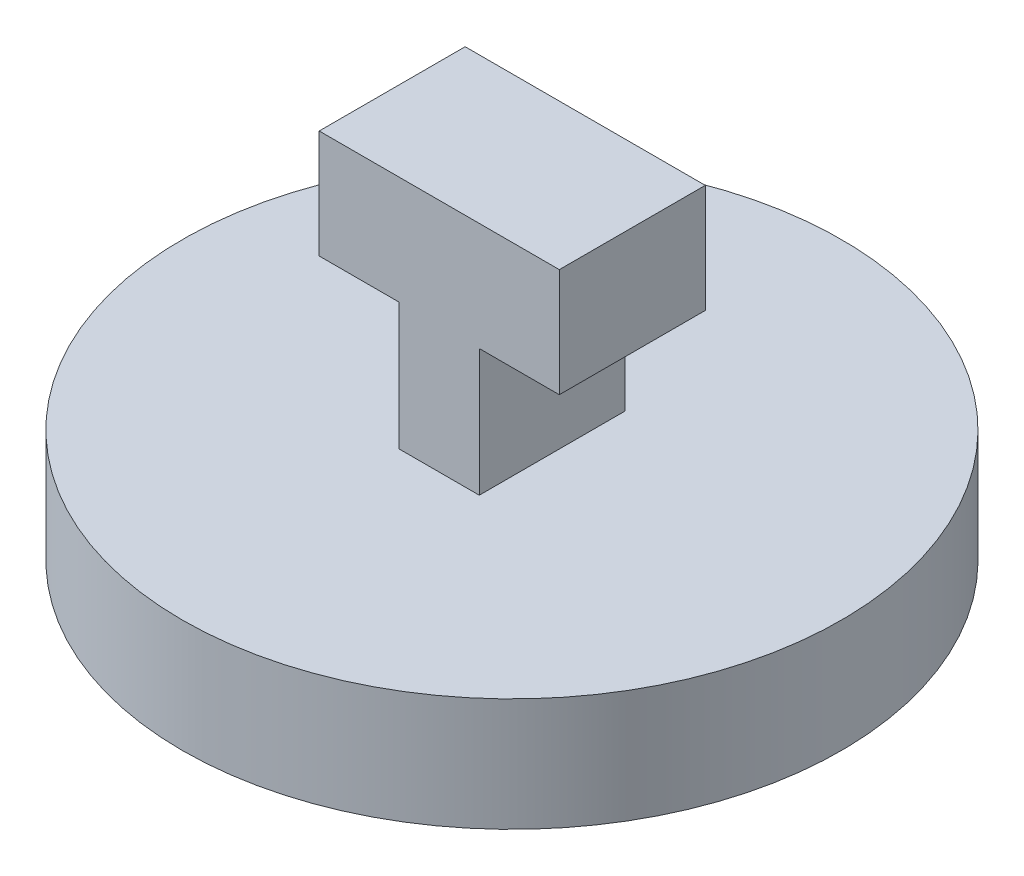
SolidWorks part; units mm, degrees
ref_plane "Front Plane" through (0, 0, 0) normal (0, 0, 1) x (1, 0, 0)
ref_plane "Top Plane" through (0, 0, 0) normal (0, 1, 0) x (1, 0, 0)
ref_plane "Right Plane" through (0, 0, 0) normal (1, 0, 0) x (0, 0, -1)
sketch "Sketch1" plane through (0, 0, 0) normal (0, 1, 0) x (1, 0, 0)
  circle A0 centre (0, 0) radius 7
  dimension "D1" = 14
extrude "Boss-Extrude1" add sketch "Sketch1" along normal blind 2.4
sketch "Sketch3" plane through (0, 0, 0) normal (0, 0, 1) x (1, 0, 0)
  line L0 (0, -0.1495) -> (0, 2.4) construction
  line L1 (7, 2.4) -> (-7, 2.4) construction
  line L2 (0, 2.4) -> (-0.8434, 2.4)
  line L3 (-0.8434, 2.4) -> (-0.8434, 5.1)
  line L4 (-0.8434, 5.1) -> (-2.5434, 5.1)
  line L5 (-2.5434, 5.1) -> (-2.5434, 7.4)
  line L6 (-2.5434, 7.4) -> (2.5566, 7.4)
  line L7 (2.5566, 7.4) -> (2.5566, 5.0986)
  line L8 (2.5566, 5.0986) -> (0.8566, 5.0986)
  line L9 (0.8566, 2.4) -> (-0.8434, 2.4)
  line L10 (0.8566, 2.4) -> (0.8566, 5.0986)
  dimension "D1" = 1.7
  dimension "D2" = 1.7
  dimension "D3" = 1.7
  dimension "D4" = 2.7
  dimension "D5" = 2.3
extrude "Boss-Extrude3" add sketch "Sketch3" along normal blind 1.55 and the other way blind 1.55 contours L9 L10 L8 L7 L6 L5 L4 L3 L2 region at (0.0068, 5.5468, 0)
